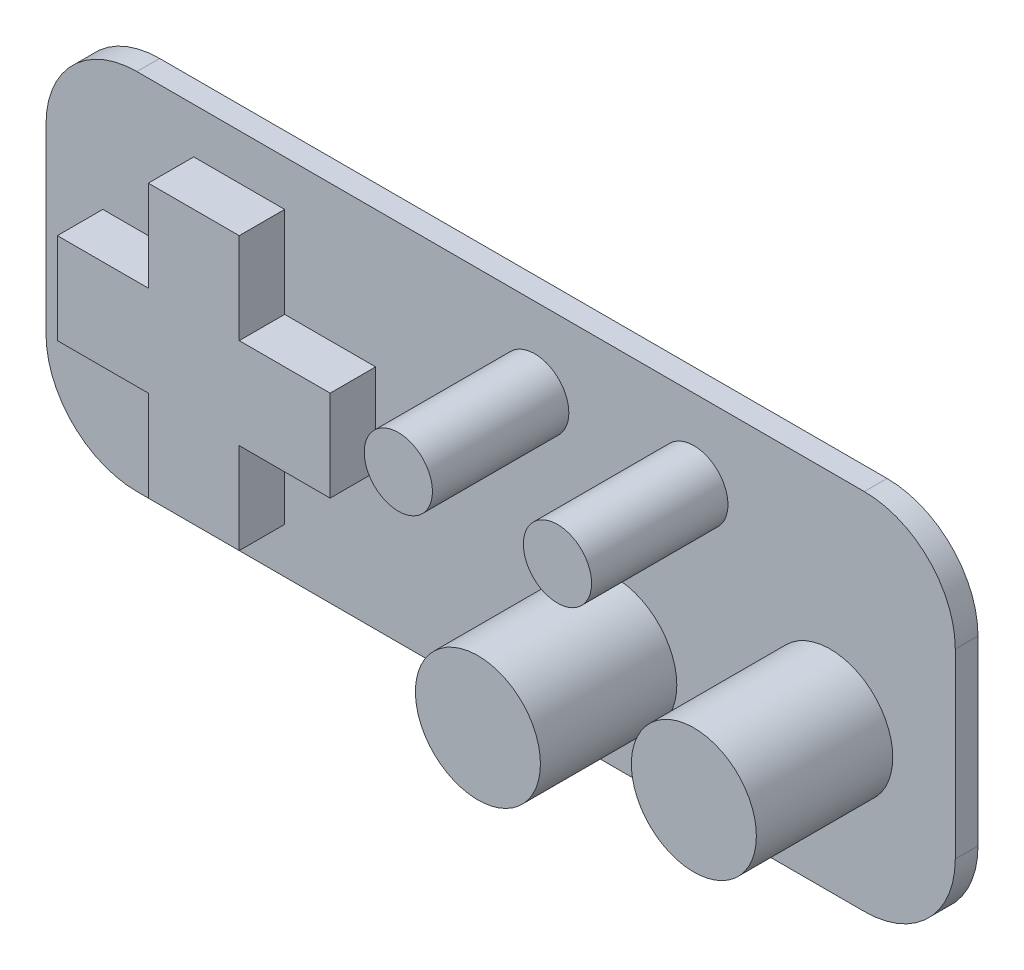
SolidWorks part; units mm, degrees
ref_plane "前视基准面" through (0, 0, 0) normal (0, 0, 1) x (1, 0, 0)
ref_plane "上视基准面" through (0, 0, 0) normal (0, 1, 0) x (1, 0, 0)
ref_plane "右视基准面" through (0, 0, 0) normal (1, 0, 0) x (0, 0, -1)
sketch "草图1" plane through (0, 0, 0) normal (0, 0, 1) x (1, 0, 0)
  line L1 (-15.7826, 8.75) -> (16.2174, 8.75)
  line L2 (-19.7826, 4.75) -> (-19.7826, -3.25)
  line L3 (-15.7826, -7.25) -> (16.2174, -7.25)
  line L4 (20.2174, 4.75) -> (20.2174, -3.25)
  arc A0 (-15.7826, 8.75) -> (-19.7826, 4.75) centre (-15.7826, 4.75) ccw
  arc A1 (16.2174, 8.75) -> (20.2174, 4.75) centre (16.2174, 4.75) cw
  arc A2 (16.2174, -7.25) -> (20.2174, -3.25) centre (16.2174, -3.25) ccw
  arc A3 (-19.7826, -3.25) -> (-15.7826, -7.25) centre (-15.7826, -3.25) ccw
  point P6 (-19.7826, 8.75)
  point P9 (20.2174, 8.75)
  point P14 (-19.7826, -7.25)
  dimension "D3" = 4
  dimension "D4" = 4
  dimension "D1" = 40
  dimension "D2" = 16
extrude "凸台-拉伸1" add sketch "草图1" along normal blind 1
sketch "草图3" plane through (0, 0, 1) normal (0, 0, 1) x (1, 0, 0)
  line L0 (-15.7826, -7.25) -> (16.2174, -7.25) construction
  line L1 (20.2174, -3.25) -> (20.2174, 4.75) construction
  line L2 (-13.2826, 6.75) -> (-13.2826, 2.75)
  line L3 (-13.2826, 2.75) -> (-17.2826, 2.75)
  line L4 (-17.2826, 2.75) -> (-17.2826, -1.25)
  line L5 (-17.2826, -1.25) -> (-13.2826, -1.25)
  line L6 (-13.2826, -1.25) -> (-13.2826, -5.25)
  line L7 (-13.2826, -5.25) -> (-9.2826, -5.25)
  line L8 (-9.2826, -5.25) -> (-9.2826, -1.25)
  line L9 (-9.2826, -1.25) -> (-5.2826, -1.25)
  line L10 (-5.2826, -1.25) -> (-5.2826, 2.75)
  line L11 (-5.2826, 2.75) -> (-9.2826, 2.75)
  line L12 (-9.2826, 2.75) -> (-9.2826, 6.75)
  line L13 (-9.2826, 6.75) -> (-13.2826, 6.75)
  line L14 (-11.2826, 18.1091) -> (-11.2826, -49981.8909) construction
  line L15 (-1013.0365, 0.75) -> (48986.9635, 0.75) construction
  circle A0 centre (5.2174, -2.75) radius 2.75
  circle A1 centre (14.7174, -0.75) radius 2.75
  circle A2 centre (1.7174, 5.25) radius 1.5
  circle A3 centre (8.7174, 5.25) radius 1.5
  point P27 (-11.2826, 0.75)
  dimension "D1" = 5.5
  dimension "D3" = 4.5
  dimension "D5" = 15
  dimension "D6" = 3
  dimension "D2" = 9.5
  dimension "D4" = 2
  dimension "D7" = 7
  dimension "D8" = 6
  dimension "D9" = 6
  dimension "D10" = 4
  dimension "D11" = 4
  dimension "D12" = 16.5
  dimension "D13" = 3.5
extrude "凸台-拉伸2" add sketch "草图3" along normal blind 6 contours A2 | A3 | A0 | A1 region at (5.2174, -2.75, 1) region at (14.7174, -0.75, 1) region at (1.7174, 5.25, 1) region at (8.7174, 5.25, 1)
sketch "草图4" plane through (0, 0, 0) normal (0, 0, 1) x (1, 0, 0)
  line L2 (-13.2826, 6.75) -> (-13.2826, 2.75)
  line L3 (-13.2826, 2.75) -> (-17.2826, 2.75)
  line L4 (-17.2826, 2.75) -> (-17.2826, -1.25)
  line L5 (-17.2826, -1.25) -> (-13.2826, -1.25)
  line L6 (-13.2826, -1.25) -> (-13.2826, -5.25)
  line L7 (-13.2826, -5.25) -> (-9.2826, -5.25)
  line L8 (-9.2826, -5.25) -> (-9.2826, -1.25)
  line L9 (-9.2826, -1.25) -> (-5.2826, -1.25)
  line L10 (-5.2826, -1.25) -> (-5.2826, 2.75)
  line L11 (-5.2826, 2.75) -> (-9.2826, 2.75)
  line L12 (-9.2826, 2.75) -> (-9.2826, 6.75)
  line L13 (-9.2826, 6.75) -> (-13.2826, 6.75)
  line L14 (-11.2826, 18.1091) -> (-11.2826, -49981.8909) construction
  line L15 (-1013.0365, 0.75) -> (48986.9635, 0.75) construction
  circle A0 centre (5.2174, -2.75) radius 2.75
  circle A1 centre (14.7174, -0.75) radius 2.75
  circle A2 centre (1.7174, 5.25) radius 1.5
  circle A3 centre (8.7174, 5.25) radius 1.5
  point P27 (-11.2826, 0.75)
  dimension "D1" = 5.5
  dimension "D6" = 3
  dimension "D2" = 9.5
  dimension "D4" = 2
  dimension "D7" = 7
  dimension "D8" = 6
  dimension "D9" = 6
  dimension "D10" = 4
  dimension "D11" = 4
  dimension "D12" = 16.5
  dimension "D13" = 3.5
extrude "凸台-拉伸3" add sketch "草图4" along normal blind 3 contours L12 L13 L2 L3 L4 L5 L6 L7 L8 L9 L10 L11 region at (-11.2826, 0.75, 0)
